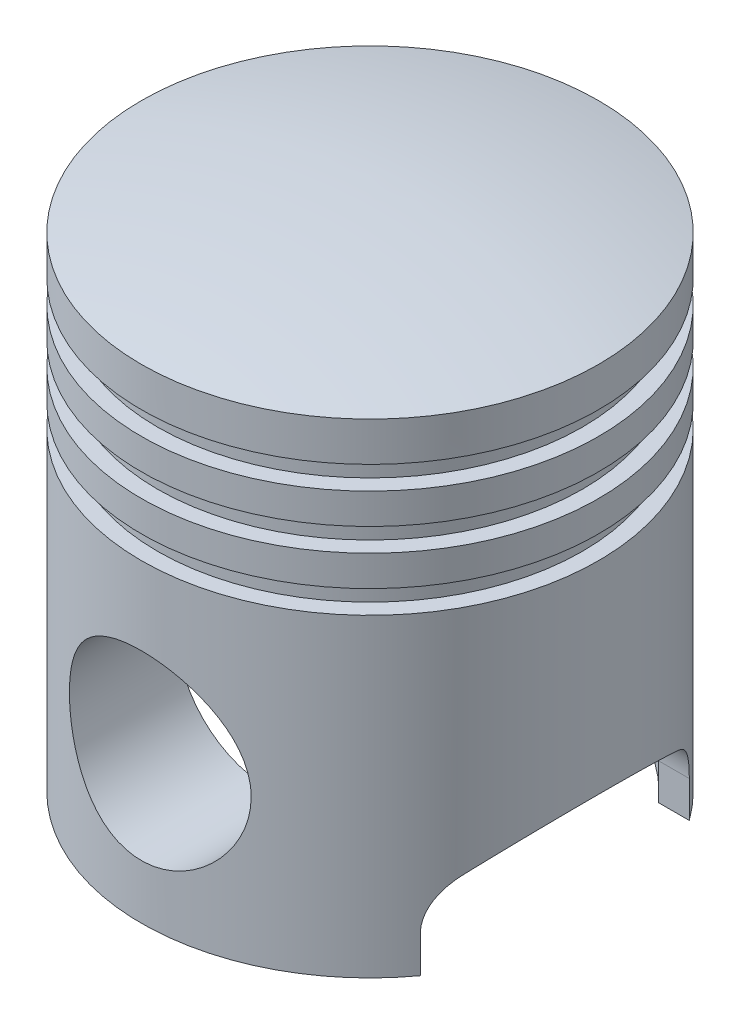
SolidWorks part; units mm, degrees
ref_plane "Front Plane" through (0, 0, 0) normal (0, 0, 1) x (1, 0, 0)
ref_plane "Top Plane" through (0, 0, 0) normal (0, 1, 0) x (1, 0, 0)
ref_plane "Right Plane" through (0, 0, 0) normal (1, 0, 0) x (0, 0, -1)
sketch "Sketch3" plane through (0, 0, 0) normal (0, 1, 0) x (1, 0, 0)
  circle A0 centre (0, 0) radius 42.5
extrude "Boss-Extrude1" add sketch "Sketch3" along normal blind 90
shell "Shell1" thickness 4.5 removed face at (0, 0, 42.5)
sketch "Sketch4" plane through (0, 90, 0) normal (0, 1, 0) x (1, 0, 0)
  circle A0 centre (0, 0) radius 39.5
extrude "Cut-Extrude2" cut sketch "Sketch4" against normal blind 4.3 from offset 7.3 flip side to cut offset against normal yes
pattern_linear "LPattern1" count 3 spacing 10 along (0, -1, 0) of "Cut-Extrude2"
dome "Dome2" faces to dome 1 distance 5 reverse direction no elliptical dome no face at (0, 90, 42.5) parameters "D1"=5
sketch "Sketch5" plane through (0, 0, 0) normal (0, 0, 1) x (1, 0, 0)
  line L0 (-42.5, 0) -> (42.5, 0) construction
  circle A0 centre (0, 27) radius 16.9
  dimension "D1" = 27
extrude "Cut-Extrude3" cut sketch "Sketch5" against normal through all both and the other way through all
sketch "Sketch10" plane through (0, 0, 0) normal (1, 0, 0) x (0, 0, -1)
  line L0 (-25, 0) -> (-25, 6.7558)
  line L1 (-42.5, 0) -> (42.5, 0) construction
  line L2 (25, 0) -> (25, 6.7558)
  arc A0 (-20, 15.416) -> (20, 15.416) centre (0, -19.225) cw
  arc A1 (25, 6.7558) -> (20, 15.416) centre (15, 6.7558) ccw
  arc A2 (-25, 6.7558) -> (-20, 15.416) centre (-15, 6.7558) cw
  point P10 (25, 12)
  point P13 (-25, 12)
  dimension "D5" = 10
  dimension "D1" = 12
  dimension "D2" = 12
  dimension "D3" = 25
  dimension "D4" = 50
extrude "Cut-Extrude4" cut sketch "Sketch10" against normal through all both and the other way through all
sketch "Sketch11" plane through (0, 0, 0) normal (0, 0, 1) x (1, 0, 0)
  circle A0 centre (0, 27) radius 16.9
  circle A1 centre (0, 27) radius 22.5
extrude "Boss-Extrude4" add sketch "Sketch11" along normal up to next from offset 19
sketch "Sketch12" plane through (0, 0, 0) normal (0, 0, 1) x (1, 0, 0)
  circle A0 centre (0, 27) radius 16.9
  circle A1 centre (0, 27) radius 22.5
extrude "Boss-Extrude5" add sketch "Sketch12" against normal up to next from offset 19 offset against normal yes
